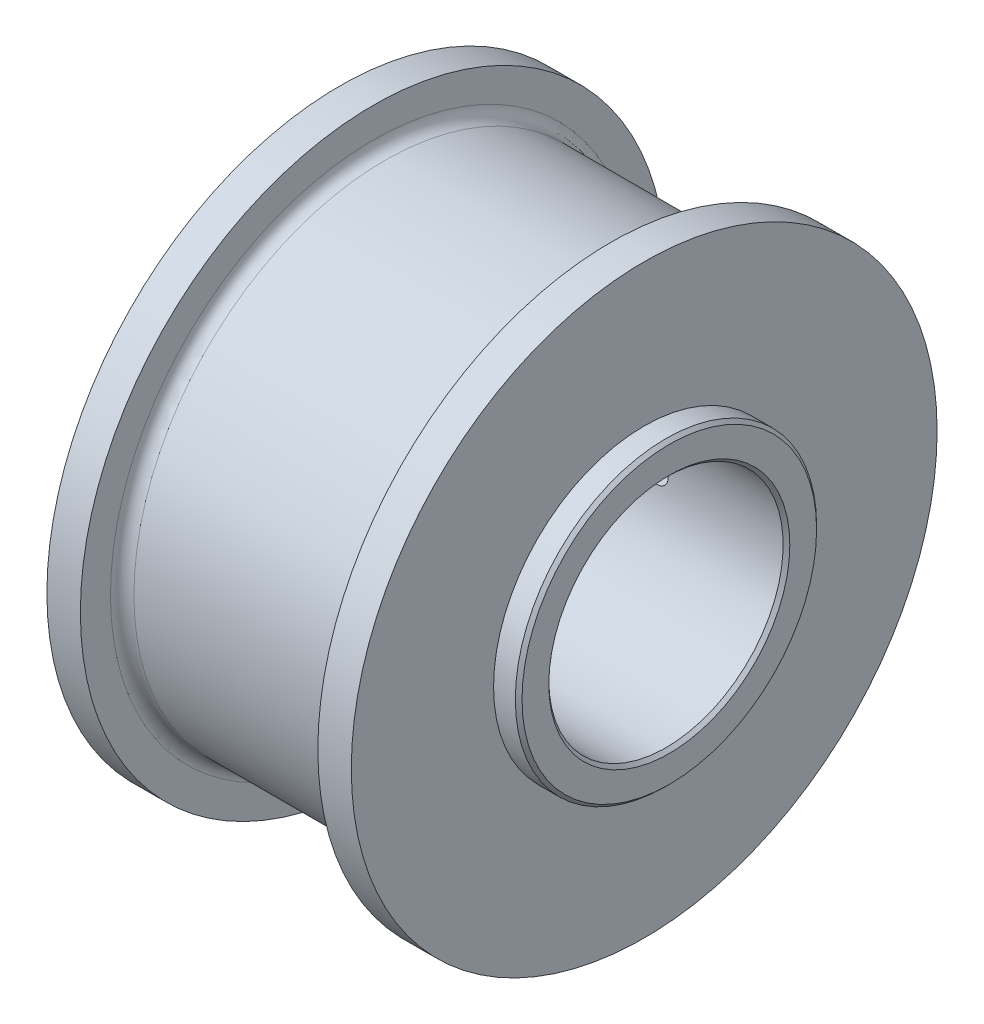
SolidWorks part; units mm, degrees
ref_plane "Front Plane" through (0, 0, 0) normal (0, 0, 1) x (1, 0, 0)
ref_plane "Top Plane" through (0, 0, 0) normal (0, 1, 0) x (1, 0, 0)
ref_plane "Right Plane" through (0, 0, 0) normal (1, 0, 0) x (0, 0, -1)
sketch "Sketch1" plane through (0, 0, 0) normal (0, 0, 1) x (1, 0, 0)
  line L0 (3.81, 44.45) -> (8.89, 44.45)
  line L1 (8.89, 44.45) -> (8.89, 38.1)
  line L3 (44.925, 38.1) -> (44.925, 44.45)
  line L4 (44.925, 44.45) -> (50.005, 44.45)
  line L5 (50.005, 44.45) -> (50.005, 22.86)
  line L6 (50.005, 22.86) -> (53.815, 22.86)
  line L7 (53.815, 22.86) -> (53.815, 17.78)
  line L8 (53.815, 17.78) -> (15.08, 17.78)
  line L9 (15.08, 17.78) -> (15.08, 16.002)
  line L10 (15.08, 16.002) -> (5.08, 16.002)
  line L11 (5.08, 16.002) -> (5.08, 11.08)
  line L12 (5.08, 11.08) -> (0, 11.08)
  line L13 (0, 11.08) -> (0, 22.86)
  line L14 (0, 22.86) -> (3.81, 22.86)
  line L15 (3.81, 22.86) -> (3.81, 44.45)
  line L16 (0, 0) -> (18.9296, 0) construction
  line L18 (8.89, 38.1) -> (44.925, 38.1)
  point P19 (9.4648, 0)
  dimension "D2" = 10
  dimension "D3" = 38.735
  dimension "D1" = 16.002
  dimension "D5" = 17.78
  dimension "D6" = 22.86
  dimension "D7" = 22.86
  dimension "D8" = 5.08
  dimension "D9" = 44.45
  dimension "D10" = 44.45
  dimension "D14" = 3.81
  dimension "D15" = 3.81
  dimension "D16" = 5.08
  dimension "D11" = 38.1
  dimension "D12" = 11.08
revolve "Revolve1" add sketch "Sketch1" angle 360 about L16
ref_plane "Plane1" through (34.257, 0, 0) normal (1, 0, 0) x (0, 0, -1)
sketch "Sketch2" plane through (34.257, 0, 0) normal (1, 0, 0) x (0, 0, -1)
  point P0 (0, 0)
ref_plane "Plane2" through (0, 0, -38.1) normal (0, 0, -1) x (-1, 0, 0)
sketch "Sketch3" plane through (0, 0, -38.1) normal (0, 0, -1) x (-1, 0, 0)
  line L0 (0, 0) -> (-24.097, 0) construction
  line L1 (-44.417, 25.4) -> (-24.097, 25.4)
  line L2 (-44.417, 25.4) -> (-44.417, -25.4)
  line L3 (-44.417, -25.4) -> (-24.097, -25.4)
  line L4 (-24.097, 25.4) -> (-24.097, -25.4)
  line L5 (-34.257, 0) -> (-34.257, 25.4) construction
  point P4 (0, 0)
  point P8 (-34.257, 0)
  dimension "D1" = 50.8
  dimension "D2" = 20.32
extrude "Cut-Extrude1" cut sketch "Sketch3" against normal blind 2.54
sketch "Sketch4" plane through (0, 0, -38.1) normal (0, 0, -1) x (-1, 0, 0)
  point P0 (-34.257, 0)
hole_wizard "1/8 (0.125) Diameter Hole1" positions "Sketch4" profile "Sketch5" hole size "1/8" standard "ANSI Inch" end condition up to next
sketch "Sketch5" plane through (34.257, 0, -38.1) normal (1, 0, 0) x (0, 1, 0)
  line L0 (0, 0) -> (0, 20.32)
  line L1 (0, 20.32) -> (1.5875, 20.32)
  line L2 (1.5875, 20.32) -> (1.5875, 0)
  line L5 (1.5875, 0) -> (0, 0)
  line L11 (0, -6.35) -> (0, 107.95) construction
  dimension "Thru Hole Dia." = 3.175
  dimension "Thru Hole Depth" = 20.32
fillet "Fillet2" radius 1.778 2 edges at (8.89, 0, 38.1) (44.925, 0, 38.1)
chamfer "Chamfer1" distance 0.508 4 edges at (0, 0, 22.86) (53.815, 0, 22.86) (53.815, 0, 17.78) (0, 0, 11.08)
equation "\"bearing_radius\"= 0.629921"
equation "\"bearing_width\"=0.393701"
equation "\"D2@Sketch1\"=\"bearing_width\""
equation "\"kero_radius\"=0.23622in"
equation "\"lox_radius\"=0.23622in"
equation "\"Cavity_width\"=0.031in"
equation "\"tooth_width\"=0.01in"
equation "\"cavity_depth\"=0.031in"
equation "\"seal_step\"=0.01in"
equation "\"purge_length\"=0.04in"
equation "\"insert_radius\" = 0.7in"
equation "\"recycle_groove width\" = 0.06in"
equation "\"recycle_groove_depth\" = 0.06in"
equation "\"N2_purge_width\"= .06in"
equation "\"N2_purge_depth\"= .06in"
equation "\"drain_width\"= .06in"
equation "\"drain_depth\"= .06in"
equation "\"radial_clearance\"= .002in"
equation "\"IPS_flange_width\"= .2in"
equation "\"IPS_flange_radius\" = 1.75in"
equation "\"IPS_LOX_male_radius\"= .9in"
equation "\"IPS_Kero_male_radius\" = .9in"
equation "\"IPS_radius\"= 1.5in"
equation "\"D5@Sketch1\"=\"insert_radius\""
equation "\"InsertLength\"= 1.525in"
equation "\"D3@Sketch1\"=\"InsertLength\""
equation "\"D6@Sketch1\"=\"IPS_Kero_male_radius\""
equation "\"D7@Sketch1\"=\"IPS_LOX_male_radius\""
equation "\"D8@Sketch1\"=\"IPS_flange_width\""
equation "\"D9@Sketch1\"=\"IPS_flange_radius\""
equation "\"D10@Sketch1\"=\"IPS_flange_radius\""
equation "\"D12@Sketch1\"=\"lox_radius\"+.2"
equation "\"D11@Sketch1\"=\"IPS_radius\""
